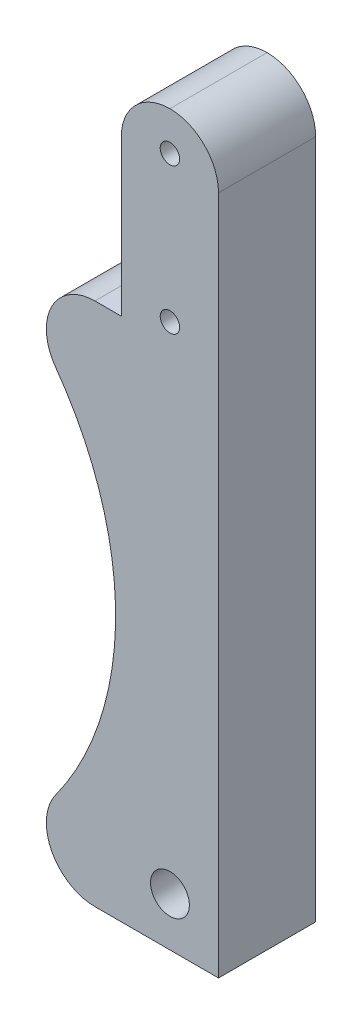
SolidWorks part; units mm, degrees
ref_plane "Front" through (0, 0, 0) normal (0, 0, 1) x (1, 0, 0)
ref_plane "Top" through (0, 0, 0) normal (0, 1, 0) x (1, 0, 0)
ref_plane "Right" through (0, 0, 0) normal (1, 0, 0) x (0, 0, -1)
sketch "Esquisse1" plane through (0, 0, 0) normal (0, 0, 1) x (1, 0, 0)
  line L1 (0, 0) -> (10, 0)
  line L2 (0, 0) -> (0, 75)
  line L3 (0, 75) -> (10, 75)
  line L4 (10, 0) -> (10, 75)
  dimension "D1" = 10
  dimension "D2" = 75
extrude "Boss.-Extru.1" add sketch "Esquisse1" along normal blind 10
sketch "Esquisse2" plane through (0, 0, 10) normal (0, 0, 1) x (1, 0, 0)
  line L0 (5, 75) -> (5, 56) construction
  line L1 (10, 75) -> (0, 75) construction
  line L2 (0, 0) -> (10, 0) construction
  line L3 (5, 5) -> (5, 0) construction
  circle A0 centre (5, 56) radius 1
  circle A1 centre (5, 71) radius 1
  circle A2 centre (5, 5) radius 2
  point P11 (5, 0)
  dimension "D1" = 15
  dimension "D2" = 4
  dimension "D3" = 2
  dimension "D4" = 4
  dimension "D5" = 5
extrude "Enlèv. mat.-Extru.1" cut sketch "Esquisse2" against normal up to vertex (10 mm away) up to point (0, 75, 0)
fillet "Congé1" radius 5 2 edges at (10, 75, 5) (0, 75, 5)
sketch "Esquisse3" plane through (0, 0, 10) normal (0, 0, 1) x (1, 0, 0)
  line L0 (0, 0) -> (-15, 0)
  line L1 (0, 0) -> (0, 54)
  line L2 (0, 70) -> (0, 0) construction
  line L3 (0, 54) -> (-15, 54)
  line L4 (-15, 0) -> (-15, 54) construction
  arc A0 (-15, 54) -> (-15, 0) centre (-33.0901, 27) cw
  point P8 (0, 0)
  point P9 (-33.2425, 26.8972)
  dimension "D1" = 32.5
  dimension "D3" = 15
  dimension "D2" = 54
extrude "Boss.-Extru.2" add sketch "Esquisse3" against normal up to vertex (10 mm away) up to point (0, 0, 0)
fillet "Congé2" radius 5 2 edges at (-15, 54, 5) (-15, 0, 5)
